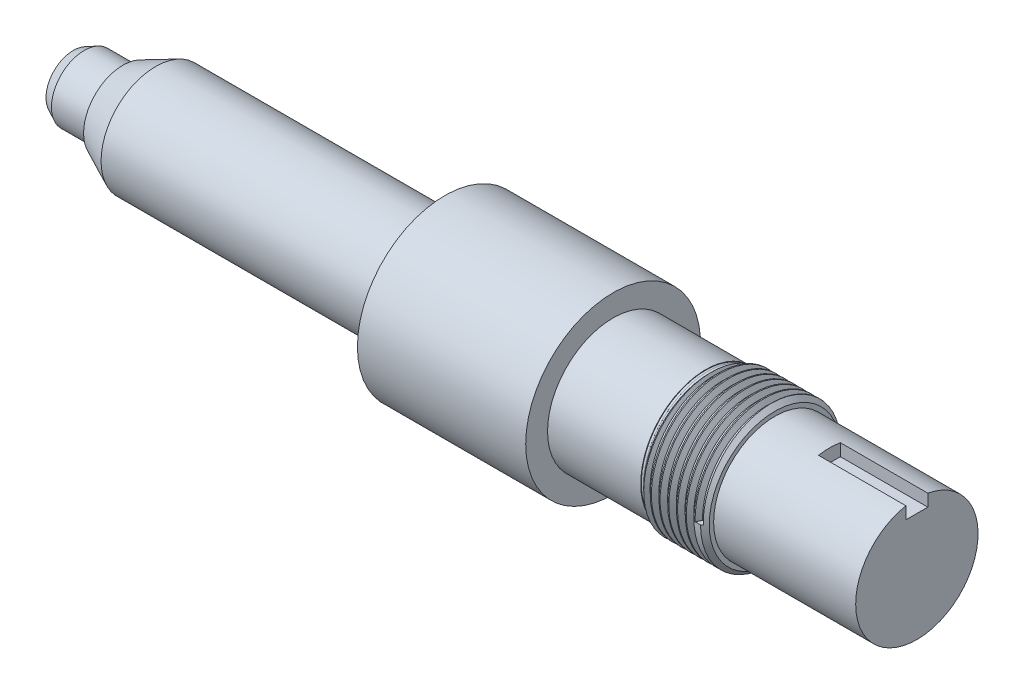
SolidWorks part; units mm, degrees
ref_plane "Front" through (0, 0, 0) normal (0, 0, 1) x (1, 0, 0)
ref_plane "Top" through (0, 0, 0) normal (0, 1, 0) x (1, 0, 0)
ref_plane "Right" through (0, 0, 0) normal (1, 0, 0) x (0, 0, -1)
sketch "Çizim1" plane through (0, 0, 0) normal (0, 0, 1) x (1, 0, 0)
  line L0 (0, 0) -> (0, 28)
  line L1 (0, 28) -> (-45, 28)
  line L2 (-45, 28) -> (-45, 32)
  line L3 (-45, 32) -> (-75, 32)
  line L4 (-75, 32) -> (-75, 30)
  line L7 (-366, 0) -> (0, 0)
  line L8 (-75, 30) -> (-119, 30)
  line L9 (-119, 30) -> (-119, 40)
  line L10 (-119, 40) -> (-196, 40)
  line L11 (-196, 40) -> (-196, 25)
  line L12 (-196, 25) -> (-328.3, 25)
  line L14 (-343.3, 18) -> (-343.3, 15)
  line L17 (-328.3, 25) -> (-343.3, 18)
  line L20 (-361, 15) -> (-366, 12.5)
  line L21 (-361, 15) -> (-343.3, 15)
  line L22 (-366, 12.5) -> (-366, 0)
  dimension "D1" = 32
  dimension "D2" = 28
  dimension "D3" = 30
  dimension "D4" = 30
  dimension "D5" = 45
  dimension "D6" = 44
  dimension "D7" = 40
  dimension "D8" = 25
  dimension "D9" = 77
  dimension "D10" = 224.3
  dimension "D11" = 15
  dimension "D12" = 366
  dimension "D13" = 15
  dimension "D14" = 18
  dimension "D15" = 5
  dimension "D17" = 12.5
revolve "Döndür1" add sketch "Çizim1" angle 360 about L7
chamfer "Pah1" distance 2 angle 45 2 edges at (-75, 0, 32) (-45, 0, 32)
thread "Diş1" pitch 4 method cut profile "Diş Profili1" start angle 0, offset 1, length 30, pitch 4, diameter 64
ref_plane "Düzlem1" through (-46, 0, 32) normal (0, -1, 0) x (0, 0, 1)
sketch "Diş Profili1" plane through (-46, 0, 32) normal (0, -1, 0) x (0, 0, 1)
  line L0 (0, 0) -> (0, 4) construction
  line L11 (0, 0) -> (0, 3.5)
  line L12 (0, 3.5) -> (-2.1651, 2.25)
  line L13 (-2.1651, 2.25) -> (-2.1651, 1.25)
  line L15 (-2.1651, 1.25) -> (0, 0)
  line L17 (-2.1651, 1.75) -> (0, 1.75) construction
  point P2 (0, 0)
  dimension "Pitch" = 4
  dimension "Profile_Angle" = 60
  dimension "Profile_Land" = 1
  dimension "Profile_Height" = 2.1651
sketch "Çizim6" plane through (0, 0, 0) normal (1, 0, 0) x (0, 0, -1)
  line L1 (-5, 35.9755) -> (5, 35.9755)
  line L2 (-5, 35.9755) -> (-5, 22)
  line L3 (-5, 22) -> (5, 22)
  line L4 (5, 35.9755) -> (5, 22)
  dimension "D1" = 10
  dimension "D2" = 5
  dimension "D3" = 22
extrude "Kes-Ekstrüzyon1" cut sketch "Çizim6" against normal blind 20
sketch "Çizim7" plane through (0, 0, 0) normal (1, 0, 0) x (0, 0, -1)
  line L3 (5, 22) -> (-5, 22)
  line L4 (-5, 22) -> (-5, 27.55)
  line L5 (5, 27.55) -> (5, 22)
  line L6 (5, 22) -> (-5, 22)
  line L7 (-5, 22) -> (-5, 27.55)
  line L8 (5, 27.55) -> (5, 22)
  arc A1 (-5, 27.55) -> (5, 27.55) centre (0, 0) ccw
  arc A2 (-5, 27.55) -> (5, 27.55) centre (0, 0) ccw
  dimension "D1" = 0
extrude "Yükseklik-Ekstrüzyon1" add sketch "Çizim7" along normal blind 20
